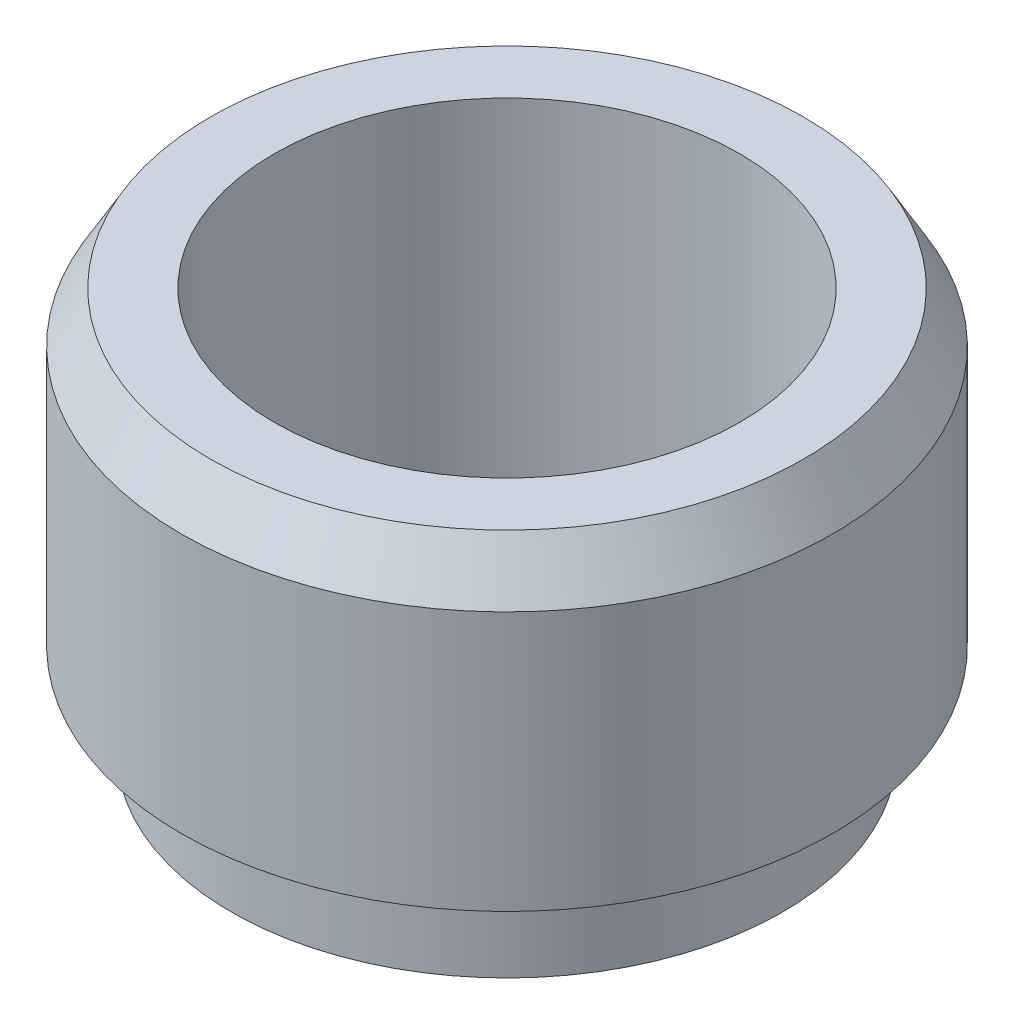
SolidWorks part; units mm, degrees
ref_plane "Front Plane" through (0, 0, 0) normal (0, 0, 1) x (1, 0, 0)
ref_plane "Top Plane" through (0, 0, 0) normal (0, 1, 0) x (1, 0, 0)
ref_plane "Right Plane" through (0, 0, 0) normal (1, 0, 0) x (0, 0, -1)
sketch "Sketch1" plane through (0, 0, 0) normal (0, 1, 0) x (1, 0, 0)
  circle A0 centre (0, 0) radius 25.875
  dimension "D1" = 51.75
extrude "Boss-Extrude1" add sketch "Sketch1" along normal blind 32
sketch "Sketch2" plane through (0, 32, 0) normal (0, 1, 0) x (1, 0, 0)
  circle A0 centre (0, 0) radius 18.5
  dimension "D1" = 37
extrude "Cut-Extrude1" cut sketch "Sketch2" against normal blind 32
chamfer "Chamfer1" distance 4 angle 30 1 edges at (0, 32, 25.875) first distance on face at (0, 32, 25.875)
sketch "Sketch3" plane through (0, 0, 0) normal (0, -1, 0) x (1, 0, 0)
  circle A0 centre (0, 0) radius 20.912
  circle A1 centre (0, 0) radius 29.3082
extrude "Cut-Extrude2" cut sketch "Sketch3" against normal blind 7.38
sketch "Sketch4" plane through (0, 0, 0) normal (0, -1, 0) x (1, 0, 0)
  circle A0 centre (0, 0) radius 20.912
  circle A1 centre (0, 0) radius 21.912
  dimension "D1" = 1
extrude "Boss-Extrude2" add sketch "Sketch4" against normal blind 5
